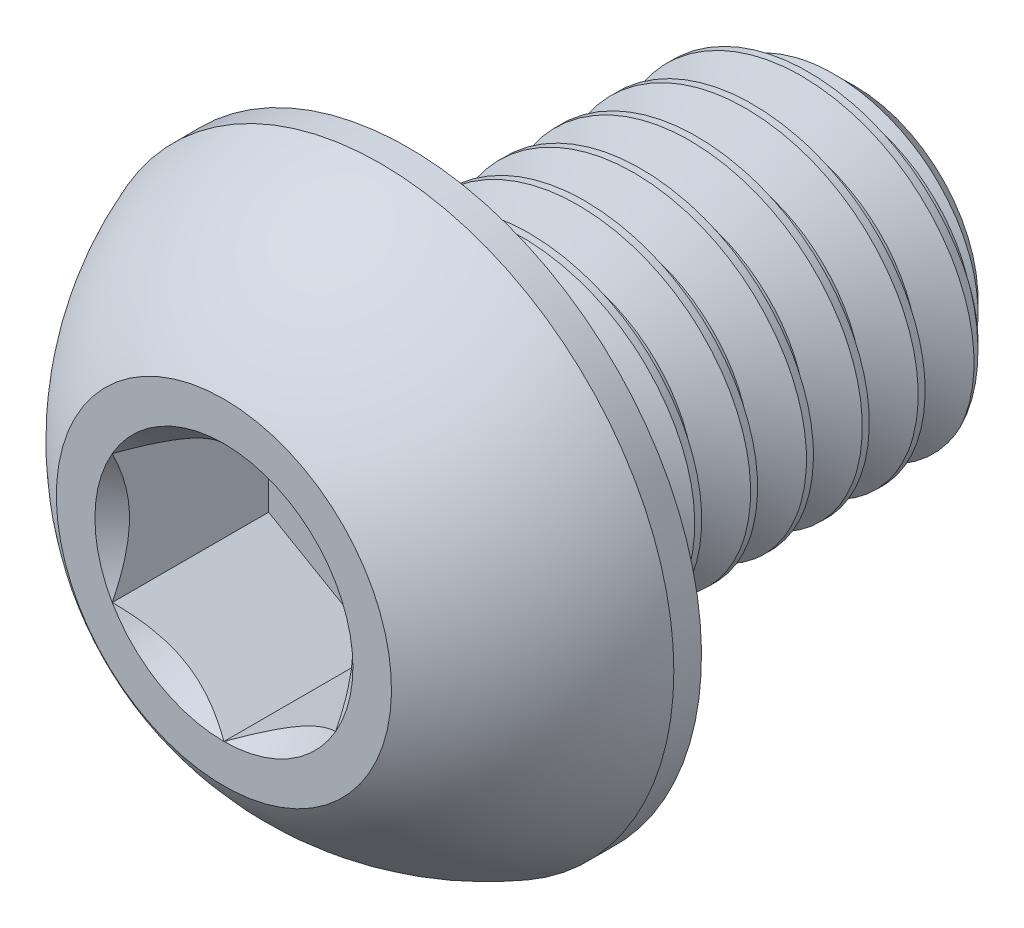
SolidWorks part; units mm, degrees
material "Plain Carbon Steel"
ref_plane "Front Plane" through (0, 0, 0) normal (0, 0, 1) x (1, 0, 0)
ref_plane "Top Plane" through (0, 0, 0) normal (0, 1, 0) x (1, 0, 0)
ref_plane "Right Plane" through (0, 0, 0) normal (1, 0, 0) x (0, 0, -1)
sketch "Sketch1" plane through (0, 0, 0) normal (1, 0, 0) x (0, 0, -1)
  line L0 (-5.65, 0) -> (5.65, 0) construction
  line L1 (-2.35, 5.25) -> (-2.35, -5.25) construction
  line L2 (5.65, 3) -> (5.65, -3) construction
  line L3 (5.5875, 3.1083) -> (6.0875, 2.2422) construction
  line L4 (6.0875, 2.2422) -> (6.5875, 3.1083) construction
  line L5 (6.5875, 3.1083) -> (5.5875, 3.1083) construction
  line L6 (5.65, 3) -> (6.525, 3) construction
  line L7 (6.0875, 3.1083) -> (6.0875, 3) construction
  line L8 (6.0875, 3) -> (6.0875, 2.3505) construction
  line L9 (6.0875, 2.3505) -> (6.0875, 2.2422) construction
  line L10 (6.025, 2.3505) -> (6.15, 2.3505)
  line L11 (5.6187, 3.0541) -> (6.5562, 3.0541)
  line L12 (6.15, 2.3505) -> (6.5562, 3.0541)
  line L13 (6.025, 2.3505) -> (5.6187, 3.0541)
  line L14 (-5.65, 2) -> (-5.65, -2) construction
  line L15 (5.65, 3) -> (-2.35, 3) construction
  point P3 (-2.35, 0)
  point P6 (-2.85, 0)
  point P21 (6.0875, 3.0541)
  point P24 (-2.845, 5.25)
  point P25 (3.15, -3)
  point P26 (-5.65, 3)
  dimension "Head Height" = 3.3
  dimension "Length" = 8
  dimension "Head Dia" = 10.5
  dimension "Thread Dia" = 6
  dimension "Pitch" = 1
  dimension "Drive Size" = 4
  dimension "D1" = 2.8
  dimension "D3" = 0.495
  dimension "D4" = 2.5
sketch "Sketch2" plane through (0, 0, 0) normal (1, 0, 0) x (0, 0, -1)
  line L0 (-5.65, 0) -> (5.65, 0)
  line L1 (5.65, 0) -> (5.65, 2.2)
  line L2 (5.65, 3) -> (5.65, -3) construction
  line L3 (5.65, 2.2) -> (4.85, 3)
  line L4 (4.85, 3) -> (-2.35, 3)
  line L5 (-2.35, 5.25) -> (-2.35, -5.25) construction
  line L6 (-2.35, 3) -> (-2.35, 5.25)
  line L7 (-2.35, 5.25) -> (-2.845, 5.25)
  line L8 (5.65, 3) -> (6.525, 3) construction
  line L9 (-5.65, 0) -> (-5.65, 3)
  arc A0 (-5.65, 3) -> (-2.845, 5.25) centre (-0.9387, 0) cw
  dimension "D1" = 0.8
  dimension "D2" = 45
revolve "Revolve1" add sketch "Sketch2" angle 360 about L0
sketch "Sketch3" plane through (0, 0, 5.65) normal (0, 0, 1) x (1, 0, 0)
  line L1 (0, 2.3094) -> (-2, 1.1547)
  line L2 (-2, 1.1547) -> (-2, -1.1547)
  line L3 (-2, -1.1547) -> (0, -2.3094)
  line L4 (0, -2.3094) -> (2, -1.1547)
  line L5 (2, -1.1547) -> (2, 1.1547)
  line L6 (2, 1.1547) -> (0, 2.3094)
  circle A0 centre (0, 0) radius 2 construction
  dimension "D1" = 4
extrude "Cut-Extrude1" cut sketch "Sketch3" against normal up to vertex (2.8 mm away) up to point (0, 0, 2.85)
sketch "Sketch4" plane through (0, 0, 5.65) normal (0, 0, 1) x (1, 0, 0)
  circle A0 centre (0, 0) radius 2.3094
extrude "Cut-Extrude2" cut sketch "Sketch4" against normal blind 10 draft 45
split "Split1" bodies to split 106 resulting bodies 107 108 split by face at (0, -5.25, 2.35)
sketch "Sketch5" plane through (0, 0, -5.65) normal (0, 0, -1) x (-1, 0, 0)
  circle A0 centre (0, 0) radius 3 construction
  circle A1 centre (0, 0) radius 3
curve "Helix/Spiral1" pitch 1 height 9 radius 3 centre (0, 0, -5.65) axis (0, 0, 1) start towards (0, 1, 0)
sketch "Sketch6" plane through (0, 0, 0) normal (1, 0, 0) x (0, 0, -1)
  line L0 (6.025, 2.3505) -> (6.15, 2.3505) construction
  line L1 (6.025, 2.3505) -> (5.6187, 3.0541) construction
  line L2 (5.6187, 3.0541) -> (6.5562, 3.0541) construction
  line L3 (6.15, 2.3505) -> (6.5562, 3.0541) construction
  line L4 (6.025, 2.3505) -> (6.15, 2.3505)
  line L5 (6.025, 2.3505) -> (5.6187, 3.0541)
  line L6 (5.6187, 3.0541) -> (6.5562, 3.0541)
  line L7 (6.15, 2.3505) -> (6.5562, 3.0541)
sweep "Cut-Sweep1" cut profiles "Sketch6" path "Helix/Spiral1" align with end faces yes
sketch "Sketch7" plane through (0, 0, 2.35) normal (0, 0, -1) x (-1, 0, 0)
  circle A1 centre (0, 0) radius 3
  circle A2 centre (0, 0) radius 3
  dimension "D1" = 0
extrude "Boss-Extrude1" add sketch "Sketch7" along normal blind 10 draft 30
equation "\"D2@Sketch1\" = \"Pitch@Sketch1\" / 8"
equation "\"D1@Sketch1\"=\"Drive Size@Sketch1\"*.7"
equation "\"D3@Sketch1\"=\"Head Height@Sketch1\"*.15"
equation "\"D1@Sketch2\"=\"Pitch@Sketch1\"*.8"
equation "\"D1@Sketch3\"=\"Drive Size@Sketch1\""
equation "\"D4@Helix/Spiral1\"=\"Pitch@Sketch1\""
equation "\"D3@Helix/Spiral1\"=\"Length@Sketch1\"+\"Pitch@Sketch1\""
equation "\"D4@Sketch1\"=\"Pitch@Sketch1\"*2.5"
